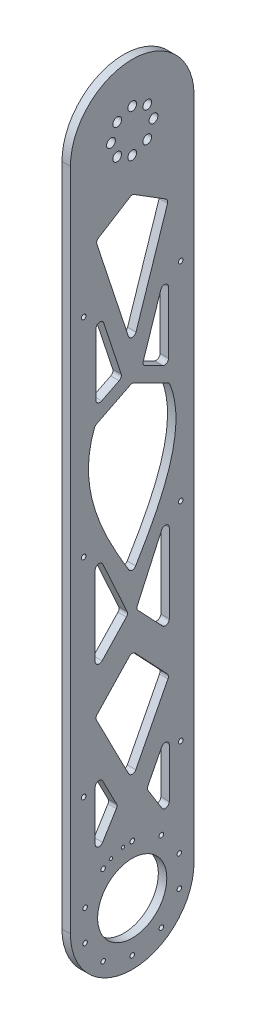
SolidWorks part; units mm, degrees
material "1060 Alloy"
ref_plane "Front Plane" through (0, 0, 0) normal (0, 0, 1) x (1, 0, 0)
ref_plane "Top Plane" through (0, 0, 0) normal (0, 1, 0) x (1, 0, 0)
ref_plane "Right Plane" through (0, 0, 0) normal (1, 0, 0) x (0, 0, -1)
sketch "Sketch1" plane through (0, 0, 0) normal (1, 0, 0) x (0, -1, 0)
  line L0 (0, 0) -> (500, 0) construction
  line L1 (0, 46.5) -> (500, 46.5)
  line L2 (0, -46.5) -> (500, -46.5)
  arc A0 (0, 46.5) -> (0, -46.5) centre (0, 0) ccw
  arc A1 (500, -46.5) -> (500, 46.5) centre (500, 0) ccw
  circle A2 centre (0, 0) radius 16 construction
  circle A3 centre (-16, 0) radius 3.3
  circle A4 centre (-11.3137, 11.3137) radius 3.3
  circle A5 centre (0, 16) radius 3.3
  circle A6 centre (11.3137, 11.3137) radius 3.3
  circle A7 centre (16, 0) radius 3.3
  circle A8 centre (11.3137, -11.3137) radius 3.3
  circle A27 centre (500, 0) radius 37.25 construction
  circle A28 centre (537.25, 0) radius 1.7
  circle A29 centre (500, 0) radius 37.25 construction
  circle A30 centre (537.25, 0) radius 1.7
  circle A31 centre (530.1359, -21.895) radius 1.7
  circle A32 centre (511.5109, -35.4269) radius 1.7
  circle A33 centre (488.4891, -35.4269) radius 1.7
  circle A34 centre (469.8641, -21.895) radius 1.7
  circle A35 centre (462.75, 0) radius 1.7
  circle A36 centre (469.8641, 21.895) radius 1.7
  circle A37 centre (488.4891, 35.4269) radius 1.7
  circle A38 centre (511.5109, 35.4269) radius 1.7
  circle A39 centre (530.1359, 21.895) radius 1.7
  circle A40 centre (500, 0) radius 26
  circle A41 centre (0, -16) radius 3.3
  circle A42 centre (-11.3137, -11.3137) radius 3.3
  point P3 (250, 0)
  point P25 (0, 0)
  point P52 (500, 0)
  point P61 (500, 0)
  dimension "D3" = 32
  dimension "D4" = 6.6
  dimension "D2" = 74.5
  dimension "D7" = 3.4
  dimension "D8" = 3.4
  dimension "D10" = 52
  dimension "D6" = 46.5
  dimension "D1" = 500
  dimension "D5" = 8
  dimension "D9" = 10
extrude "Boss-Extrude1" add sketch "Sketch1" along normal blind 6.35 contours L2 A1 L1 A0 A40 A39 A38 A37 A36 A35 A34 A33 A32 A31 A28 A8 A7 A6 A5 A4 A3 region at (0, -240.4496, 0)
ref_axis "Axis1" through (6.35, -500, 0) along (-1, 0, 0)
sketch "Sketch3" plane through (6.35, 0, 0) normal (1, 0, 0) x (0, 0, -1)
  line L0 (0, -500) -> (0, 0) construction
  line L1 (0, -422.848) -> (27.8582, -368.6328)
  line L2 (0, -422.848) -> (-27.8582, -368.6328)
  line L3 (-27.8582, -368.6328) -> (0, -339.1393)
  line L4 (0, -339.1393) -> (27.8582, -368.6328)
  line L5 (0, -41.3687) -> (-27.3129, -58.4352)
  line L6 (-27.3129, -58.4352) -> (0, -141.249)
  line L7 (0, -141.249) -> (27.3129, -58.4352)
  line L8 (27.3129, -58.4352) -> (0, -41.3687)
  line L9 (3, -313.1891) -> (27.8582, -339.5065)
  line L10 (27.8582, -339.5065) -> (27.8582, -258.646)
  line L11 (27.8582, -258.646) -> (3, -313.1891)
  line L12 (-27.8582, -339.5065) -> (-27.8582, -258.646)
  line L13 (-3, -313.1891) -> (-27.8582, -339.5065)
  line L14 (-27.8582, -258.646) -> (-3, -313.1891)
  line L15 (-27.8582, -401.4529) -> (-11, -434.2608)
  line L16 (-11, -434.2608) -> (-27.8582, -461.4818)
  line L17 (-27.8582, -461.4818) -> (-27.8582, -401.4529)
  line L18 (11, -434.2608) -> (27.8582, -461.4818)
  line L19 (27.8582, -401.4529) -> (11, -434.2608)
  line L20 (27.8582, -461.4818) -> (27.8582, -401.4529)
  line L21 (0, -164.2489) -> (-27.8582, -178.2005)
  line L22 (0, -164.2489) -> (27.8582, -178.2005)
  line L23 (7.5, -156.821) -> (27.3129, -96.7475)
  line L24 (27.3129, -96.7475) -> (27.3129, -166.7434)
  line L25 (27.3129, -166.7434) -> (7.5, -156.821)
  line L26 (-27.3129, -96.7475) -> (-27.3129, -166.7434)
  line L27 (-7.5, -156.821) -> (-27.3129, -96.7475)
  line L28 (-27.3129, -166.7434) -> (-7.5, -156.821)
  spline S0 degree 3 poles (-27.8582, -178.2005) (-43.7791, -216.0933) (-18.6166, -258.2761) (0, -289.085) knots 0 0 0 0 1 1 1 1
  spline S1 degree 3 poles (27.8582, -178.2005) (43.7791, -216.0933) (18.6166, -258.2761) (0, -289.085) knots 0 0 0 0 1 1 1 1
  dimension "D1" = 15
  dimension "D2" = 20
  dimension "D3" = 12
  dimension "D4" = 10
  dimension "D5" = 6
  dimension "D6" = 15
  dimension "D7" = 22
extrude "Cut-Extrude1" cut sketch "Sketch3" against normal through all
fillet "Fillet1" radius 3 30 edges at (3.175, -58.4352, -27.3129) (3.175, -41.3687, 0) (3.175, -58.4352, 27.3129) (3.175, -141.249, 0) (3.175, -289.085, 0) (3.175, -164.2489, 0) (3.175, -401.4529, 27.8582) (3.175, -434.2608, 11) (3.175, -461.4818, 27.8582) (3.175, -461.4818, -27.8582) (3.175, -434.2608, -11) (3.175, -401.4529, -27.8582) (3.175, -368.6328, -27.8582) (3.175, -339.1393, 0) (3.175, -368.6328, 27.8582) (3.175, -422.848, 0) (3.175, -313.1891, 3) (3.175, -339.5065, 27.8582) (3.175, -258.646, 27.8582) (3.175, -178.2005, -27.8582) (3.175, -178.2005, 27.8582) (3.175, -339.5065, -27.8582) (3.175, -313.1891, -3) (3.175, -258.646, -27.8582) (3.175, -96.7475, 27.3129) (3.175, -166.7434, 27.3129) (3.175, -156.821, 7.5) (3.175, -166.7434, -27.3129) (3.175, -156.821, -7.5) (3.175, -96.7475, -27.3129)
sketch "Sketch4" plane through (6.35, 0, 0) normal (1, 0, 0) x (0, 0, -1)
  line L0 (0, 46.5) -> (-113.1579, 46.5) construction
  line L1 (-46.5, 0) -> (-46.5, -500) construction
  line L2 (-46.5, -100) -> (46.5, -100) construction
  line L3 (46.5, 0) -> (46.5, -500) construction
  line L4 (-46.5, -106.35) -> (46.5, -106.35) construction
  line L5 (-36.5, -100) -> (-36.5, -106.35) construction
  line L6 (0, 0) -> (0, -106.35) construction
  line L7 (0, -106.35) -> (0, -256.35) construction
  line L8 (0, -256.35) -> (46.5, -256.35) construction
  line L9 (46.5, -262.7) -> (-46.5, -262.7) construction
  line L10 (0, -181.35) -> (46.5, -181.35) construction
  line L11 (0, -262.7) -> (0, -412.7) construction
  line L12 (0, -412.7) -> (46.5, -412.7) construction
  line L13 (0, -337.7) -> (46.5, -337.7) construction
  arc A1 (46.5, 0) -> (-46.5, 0) centre (0, 0) ccw construction
  circle A2 centre (-36.5, -103.175) radius 1.75
  circle A3 centre (36.5, -103.175) radius 1.75
  circle A4 centre (-36.5, -259.525) radius 1.75
  circle A5 centre (36.5, -259.525) radius 1.75
  circle A6 centre (-36.5, -415.875) radius 1.75
  circle A7 centre (36.5, -415.875) radius 1.75
  point P17 (-36.5, -103.175)
  dimension "D1" = 3.5
  dimension "D2" = 6.35
  dimension "D3" = 10
  dimension "D4" = 146.5
  dimension "D5" = 150
  dimension "D6" = 6.35
  dimension "D7" = 81.35
  dimension "D8" = 150
  dimension "D9" = 81.35
extrude "Cut-Extrude2" cut sketch "Sketch4" against normal through all
sketch "Sketch5" plane through (6.35, 0, 0) normal (1, 0, 0) x (0, 0, -1)
  line L0 (-6.9161, -463.3431) -> (-15.9511, -466.2787) construction
  line L1 (-7.2252, -475.0096) -> (7.4545, -470.2399) construction
  line L2 (-21.895, -469.8641) -> (0, -462.75) construction
  line L3 (-10.9475, -466.3071) -> (0, -500) construction
  circle A0 centre (-6.9161, -463.3431) radius 1.2
  circle A1 centre (-15.9511, -466.2787) radius 1.2
  circle A2 centre (0, -500) radius 26 construction
  circle A3 centre (0, -500) radius 26 construction
  circle A4 centre (0, -462.75) radius 1.7 construction
  circle A5 centre (-21.895, -469.8641) radius 1.7 construction
  circle A6 centre (0, -462.75) radius 1.7 construction
  circle A7 centre (-21.895, -469.8641) radius 1.7 construction
  point P16 (-11.4336, -464.8109)
  dimension "D1" = 2.4
  dimension "D2" = 9.5
  dimension "D3" = 11
extrude "Cut-Extrude4" cut sketch "Sketch5" against normal through all
equation "\"L1L\"=500"
equation "\"D1@Sketch1\"=\"L1L\""
equation "\"L1Thick\"=6.35"
equation "\"D1@Boss-Extrude1\"=\"L1Thick\""
equation "\"Harm-Drive-Outer\"=74.5"
equation "\"D2@Sketch1\"=\"Harm-Drive-Outer\""
